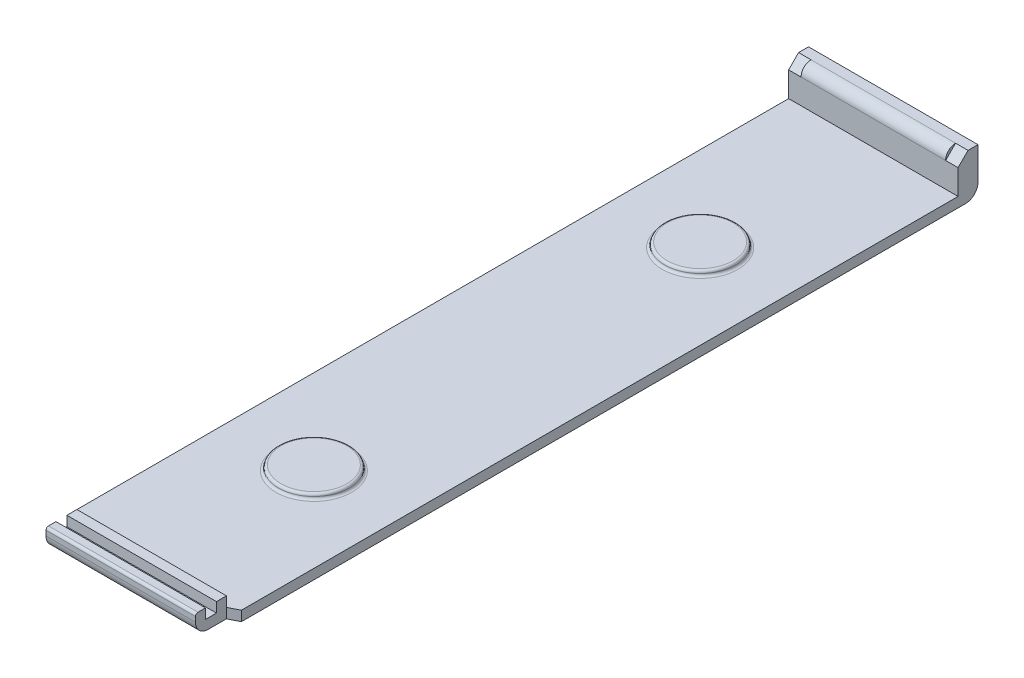
SolidWorks part; units mm, degrees
ref_plane "Front Plane" through (0, 0, 0) normal (0, 0, 1) x (1, 0, 0)
ref_plane "Top Plane" through (0, 0, 0) normal (0, 1, 0) x (1, 0, 0)
ref_plane "Right Plane" through (0, 0, 0) normal (1, 0, 0) x (0, 0, -1)
sketch "Sketch1" plane through (0, 0, 0) normal (0, 1, 0) x (1, 0, 0)
  line L1 (-19.5, 77.5) -> (19.5, 77.5)
  line L2 (-19.5, 77.5) -> (-19.5, -77.5)
  line L3 (-19.5, -77.5) -> (19.5, -77.5)
  line L4 (19.5, 77.5) -> (19.5, -77.5)
  line L5 (-19.5, 77.5) -> (19.5, -77.5) construction
  line L6 (-19.5, -77.5) -> (19.5, 77.5) construction
  point P0 (0, 0)
  dimension "D1" = 39
  dimension "D2" = 155
extrude "Boss-Extrude1" add sketch "Sketch1" along normal blind 2
sketch "Sketch2" plane through (0, 2, 0) normal (0, 1, 0) x (1, 0, 0)
  line L0 (-17.5, -75.5) -> (-17.5, -77.5)
  line L1 (-19.5, 77.5) -> (19.5, 77.5)
  line L2 (-19.5, 77.5) -> (-19.5, -77.5)
  line L3 (-19.5, -77.5) -> (19.5, -77.5)
  line L4 (19.5, 77.5) -> (19.5, -77.5)
  line L5 (-17.5, 75.5) -> (17.5, 75.5)
  line L6 (-17.5, 75.5) -> (-17.5, -75.5)
  line L7 (-17.5, -75.5) -> (17.5, -75.5)
  line L8 (17.5, 75.5) -> (17.5, -75.5)
  line L9 (-17.5, 75.5) -> (17.5, -75.5) construction
  line L10 (-17.5, -75.5) -> (17.5, 75.5) construction
  line L11 (17.5, -75.5) -> (17.5, -77.5)
  point P6 (0, 0)
  line M9 (19.5, -77.5) -> (19.5, 77.5)
  line M10 (19.5, 77.5) -> (-19.5, 77.5)
  line M11 (-19.5, 77.5) -> (-19.5, -77.5)
  line M12 (-19.5, -77.5) -> (19.5, -77.5)
  dimension "D1" = 2
  dimension "D2" = 2
extrude "Boss-Extrude2" add sketch "Sketch2" along normal blind 38 contours L8 L11 L3 L0 L6 L5 M9 M10 M11 M12 region at (-19.0983, 2, 76.5)
sketch "Sketch3" plane through (0, 2, 0) normal (0, 1, 0) x (1, 0, 0)
  line L0 (-17.5, 75.5) -> (-17.5, -77.5) construction
  line L1 (-17.5, -77.5) -> (-15.5, -77.5)
  line L2 (-17.5, -77.5) -> (-17.5, -75.5)
  line L3 (-17.5, -75.5) -> (-15.5, -75.5)
  line L4 (-15.5, -77.5) -> (-15.5, -75.5)
  line L5 (-17.5, -73.3) -> (-15.5, -73.3)
  line L6 (-17.5, -73.3) -> (-17.5, -71.3)
  line L7 (-17.5, -71.3) -> (-15.5, -71.3)
  line L8 (-15.5, -73.3) -> (-15.5, -71.3)
  line L9 (17.5, 75.5) -> (17.5, -77.5) construction
  line L10 (17.5, -77.5) -> (15.5, -77.5)
  line L11 (17.5, -77.5) -> (17.5, -75.5)
  line L12 (17.5, -75.5) -> (15.5, -75.5)
  line L13 (15.5, -77.5) -> (15.5, -75.5)
  line L14 (17.5, -73.3) -> (15.5, -73.3)
  line L15 (17.5, -73.3) -> (17.5, -71.3)
  line L16 (17.5, -71.3) -> (15.5, -71.3)
  line L17 (15.5, -73.3) -> (15.5, -71.3)
  line L18 (15.5, -75.5) -> (15.5, -73.3) construction
  line L19 (-15.5, -73.3) -> (15.5, -73.3) construction
  line L20 (-15.5, -75.5) -> (-15.5, -73.3) construction
  line L21 (-15.5, -75.5) -> (15.5, -75.5) construction
  line L22 (15.5, -71.3) -> (-15.5, -71.3) construction
  dimension "D1" = 2
  dimension "D2" = 2
  dimension "D3" = 2.2
  dimension "D4" = 2
extrude "Boss-Extrude3" add sketch "Sketch3" along normal up to surface (38 mm away) up to face at (0, 40, 0.5)
sketch "Sketch4" plane through (0, 0, -75.5) normal (0, 0, 1) x (1, 0, 0)
  line L0 (-17.5, 40) -> (-15.5, 40)
  line L1 (-17.5, 40) -> (17.5, 40) construction
  line L2 (-15.5, 40) -> (-15.5, 38)
  line L3 (-15.5, 38) -> (-17.5, 38)
  line L5 (-17.5, 38) -> (-17.5, 40)
  line L7 (-17.5, 40) -> (-17.5, 2) construction
  line L8 (-15.5, 33.8) -> (-17.5, 31.8)
  line L9 (-17.5, 31.8) -> (-17.5, 35.8)
  line L10 (-15.5, 33.8) -> (-15.5, 35.8)
  line L11 (-15.5, 35.8) -> (-17.5, 35.8)
  line L12 (0, 0) -> (0, 40) construction
  line L13 (15.5, 35.8) -> (17.5, 35.8)
  line L14 (15.5, 33.8) -> (15.5, 35.8)
  line L15 (17.5, 31.8) -> (17.5, 35.8)
  line L16 (15.5, 33.8) -> (17.5, 31.8)
  line L17 (17.5, 38) -> (17.5, 40)
  line L18 (15.5, 38) -> (17.5, 38)
  line L19 (15.5, 40) -> (15.5, 38)
  line L20 (17.5, 40) -> (15.5, 40)
  dimension "D1" = 2
  dimension "D2" = 2
  dimension "D3" = 45
  dimension "D4" = 2.2
  dimension "D5" = 2
extrude "Boss-Extrude4" add sketch "Sketch4" along normal up to surface (153 mm away) up to face at (0, 20.5, 77.5)
sketch "Sketch5" plane through (0, 2, 0) normal (0, 1, 0) x (1, 0, 0)
  line L1 (-15.5, -77.5) -> (15.5, -77.5)
  line L2 (-15.5, -77.5) -> (-15.5, -75.5)
  line L3 (-15.5, -75.5) -> (15.5, -75.5)
  line L4 (15.5, -77.5) -> (15.5, -75.5)
  line L5 (-15.5, -71.3) -> (15.5, -71.3)
  line L6 (-15.5, -71.3) -> (-15.5, -73.3)
  line L7 (-15.5, -73.3) -> (15.5, -73.3)
  line L8 (15.5, -71.3) -> (15.5, -73.3)
sketch "Sketch6" plane through (0, 0, -75.5) normal (0, 0, 1) x (1, 0, 0)
  line L0 (-17.5, 38) -> (-15.5, 38) construction
  line L1 (-17.5, 38) -> (17.5, 38)
  line L2 (-17.5, 38) -> (-17.5, 35.8)
  line L3 (-17.5, 35.8) -> (17.5, 35.8)
  line L4 (17.5, 38) -> (17.5, 35.8)
  line L5 (-17.5, 38) -> (-17.5, 35.8) construction
  line L6 (-15.5, 35.8) -> (-17.5, 35.8) construction
extrude "Cut-Extrude1" cut sketch "Sketch6" along normal through all
sketch "Sketch7" plane through (0, 2, 0) normal (0, 1, 0) x (1, 0, 0)
  line L1 (-17.5, -75.5) -> (17.5, -75.5)
  line L2 (-17.5, -75.5) -> (-17.5, -73.3)
  line L3 (-17.5, -73.3) -> (17.5, -73.3)
  line L4 (17.5, -75.5) -> (17.5, -73.3)
extrude "Cut-Extrude2" cut sketch "Sketch7" along normal through all
extrude "Boss-Extrude5" add sketch "Sketch5" along normal blind 2
sketch "Sketch8" plane through (0, 0, 0) normal (1, 0, 0) x (0, 0, -1)
  line L0 (75.5, 40) -> (73.5, 40)
  line L1 (-73.3, 40) -> (75.5, 40) construction
  line L2 (73.5, 40) -> (73.5, 38)
  line L3 (-73.3, 38) -> (75.5, 38) construction
  line L4 (73.5, 38) -> (75.5, 38)
  line L5 (75.5, 38) -> (75.5, 40)
  line L6 (75.5, 35.8) -> (73.5, 35.8)
  line L7 (-73.3, 35.8) -> (75.5, 35.8) construction
  line L8 (73.5, 35.8) -> (73.5, 33.8)
  line L9 (-71.3, 33.8) -> (75.5, 33.8) construction
  line L10 (73.5, 33.8) -> (75.5, 31.8)
  line L11 (75.5, 31.8) -> (75.5, 35.8)
  dimension "D1" = 2
extrude "Boss-Extrude6" add sketch "Sketch8" along normal up to surface and the other way up to surface up to face at (17.5, 16.9, -2.1) other way up to face at (-17.5, 16.9, -2.1)
sketch "Sketch10" plane through (-17.5, 0, 0) normal (1, 0, 0) x (0, 0, -1)
  line L1 (-75.5, 35.8) -> (-77.5, 35.8)
  line L2 (-75.5, 35.8) -> (-75.5, 38)
  line L3 (-75.5, 38) -> (-77.5, 38)
  line L4 (-77.5, 35.8) -> (-77.5, 38)
  line L5 (-73.3, 40) -> (-75.5, 40)
  line L6 (-73.3, 40) -> (-73.3, 38)
  line L7 (-73.3, 38) -> (-75.5, 38)
  line L8 (-75.5, 40) -> (-75.5, 38)
  line M1 (-75.5, 40) -> (-75.5, 38)
  line M2 (-75.5, 38) -> (-77.5, 38)
  line M3 (-77.5, 38) -> (-77.5, 35.8)
  line M4 (-77.5, 35.8) -> (-75.5, 35.8)
  line M11 (-73.3, 38) -> (-73.3, 40)
  line M12 (-73.3, 40) -> (-75.5, 40)
extrude "Boss-Extrude8" add sketch "Sketch10" along normal up to surface (2 mm away) contours L2 M4 M2 M3 | L7 M11 M12 M1 region at (-17.5, 39, 74.4) region at (-17.5, 36.9, 76.5) up to face at (-15.5, 39, -0.1)
sketch "Sketch11" plane through (17.5, 0, 0) normal (-1, 0, 0) x (0, 0, 1)
  line L1 (75.5, 35.8) -> (77.5, 35.8)
  line L2 (75.5, 35.8) -> (75.5, 38)
  line L3 (75.5, 38) -> (77.5, 38)
  line L4 (77.5, 35.8) -> (77.5, 38)
  line L5 (73.3, 40) -> (75.5, 40)
  line L6 (73.3, 40) -> (73.3, 38)
  line L7 (73.3, 38) -> (75.5, 38)
  line L8 (75.5, 40) -> (75.5, 38)
  line M2 (75.5, 35.8) -> (77.5, 35.8)
  line M3 (77.5, 35.8) -> (77.5, 38)
  line M4 (77.5, 38) -> (75.5, 38)
  line M5 (75.5, 38) -> (75.5, 40)
  line M6 (75.5, 40) -> (73.3, 40)
  line M7 (73.3, 40) -> (73.3, 38)
extrude "Boss-Extrude9" add sketch "Sketch11" along normal up to surface (2 mm away) contours L2 M2 M3 M4 | L7 M7 M5 M6 region at (17.5, 36.9, 76.5) region at (17.5, 39, 74.4) up to face at (15.5, 39, -0.1)
fillet "Fillet2" radius 2.5 17 edges at (-17.5, 16.9, 71.3) (17.5, 16.9, 71.3) (19.5, 20, 77.5) (-19.5, 20, 77.5) (-19.5, 20, -77.5) (-17.5, 16.9, -75.5) (17.5, 16.9, -75.5) (19.5, 20, -77.5) (-19.5, 40, 0) (0, 40, -77.5) (19.5, 40, 0) (0, 0, -77.5) (0, 0, 77.5) (-19.5, 0, 0) (19.5, 0, 0) (-17.5, 40, 77.5) (17.5, 40, 77.5)
sketch "Sketch13" plane through (0, 0, -77.5) normal (0, 0, -1) x (-1, 0, 0)
  line L0 (15.5, 37.5) -> (15.5, 4) construction
  line L1 (-15.5, 7) -> (15.5, 7)
  line L2 (-15.5, 7) -> (-15.5, 4)
  line L3 (-15.5, 4) -> (15.5, 4)
  line L4 (15.5, 7) -> (15.5, 4)
  dimension "D1" = 3
sketch "Sketch14" plane through (0, 0, -75.5) normal (0, 0, 1) x (1, 0, 0)
  line L1 (-18.25, 9) -> (18.25, 9)
  line L2 (-18.25, 9) -> (-18.25, 1.25)
  line L3 (-18.25, 1.25) -> (18.25, 1.25)
  line L4 (18.25, 9) -> (18.25, 1.25)
  line L5 (15.5, 7) -> (-15.5, 7) construction
  line L7 (17, 0) -> (17, 2.5) construction
  line L8 (19.5, 2.5) -> (17, 2.5) construction
  line L10 (-19.5, 2.5) -> (-17, 2.5) construction
  point P20 (17, 1.25)
  point P23 (18.25, 2.5)
  point P26 (-18.25, 2.5)
  dimension "D1" = 2
extrude "Boss-Extrude10" add sketch "Sketch14" along normal blind 2
extrude "Cut-Extrude4" cut sketch "Sketch13" against normal blind 2
fillet "Fillet3" radius 2 1 edges at (0, 9, -73.5)
fillet "Fillet4" radius 0.5 12 edges at (0, 4, -77.5) (0, 7, -77.5) (15.5, 7, -76.5) (15.5, 4, -76.5) (15.5, 5.5, -77.5) (-15.5, 4, -76.5) (-15.5, 7, -76.5) (-15.5, 5.5, -77.5) (0, 7, -75.5) (-15.5, 5.5, -75.5) (0, 4, -75.5) (15.5, 5.5, -75.5)
sketch "Sketch15" plane through (0, 0, 0) normal (0, -1, 0) x (1, 0, 0)
  line L0 (0, 77.5) -> (0, 0) construction
  line L1 (-17, 77.5) -> (17, 77.5) construction
  line L2 (0, 0) -> (0, -77.5) construction
  line L4 (17, -77.5) -> (-17, -77.5) construction
  circle A0 centre (0, 38.75) radius 5.1
  circle A1 centre (0, -38.75) radius 5.1
  dimension "D1" = 10.2
extrude "Cut-Extrude5" cut sketch "Sketch15" against normal through all
sketch "Sketch16" plane through (0, 2, 0) normal (0, 1, 0) x (1, 0, 0)
  circle A0 centre (0, 38.75) radius 7.1
  circle A1 centre (0, -38.75) radius 7.1
  circle A2 centre (0, 38.75) radius 5.1 construction
  dimension "D1" = 2
extrude "Boss-Extrude11" add sketch "Sketch16" along normal blind 1
fillet "Fillet5" radius 0.5 4 edges at (0, 2, 45.85) (0, 2, -31.65) (0, 3, 45.85) (0, 3, -31.65)
sketch "Sketch12" plane through (0, 0, -75.5) normal (0, 0, 1) x (1, 0, 0)
  line L0 (0, 0) -> (0, 40) construction
  line L1 (15.5, 40) -> (-15.5, 40) construction
  line L2 (0, 20) -> (-10, 20)
  line L3 (0, 20) -> (-9.0097, 15.6612)
  line L4 (0, 20) -> (-6.2349, 12.1817)
  line L5 (0, 20) -> (-2.2252, 10.2507)
  line L6 (0, 20) -> (2.2252, 10.2507)
  line L7 (0, 20) -> (6.2349, 12.1817)
  line L8 (0, 20) -> (9.0097, 15.6612)
  line L9 (0, 20) -> (10, 20)
  line L10 (0, 20) -> (9.0097, 24.3388)
  line L11 (0, 20) -> (6.2349, 27.8183)
  line L12 (0, 20) -> (2.2252, 29.7493)
  line L13 (0, 20) -> (-2.2252, 29.7493)
  line L14 (0, 20) -> (-6.2349, 27.8183)
  line L15 (0, 20) -> (-9.0097, 24.3388)
  circle A0 centre (0, 20) radius 10
  circle A1 centre (0, 20) radius 7.5
  circle A2 centre (0, 20) radius 5
  circle A3 centre (0, 20) radius 2.5
  point P26 (0, 20)
  dimension "D1" = 20
  dimension "D2" = 2.5
  dimension "D3" = 2.5
  dimension "D4" = 2.5
  dimension "D5" = 14
extrude "Cut-Extrude3" cut sketch "Sketch12" against normal through all contours A1 L6 A0 L7 | A1 L4 A0 L5 | A1 L2 A0 L3 | A1 L14 A0 L15 | A1 L0 A0 L13 | L0 A1 L12 A0 | A1 L10 A0 L11 | A1 L8 A0 L9 | A3 L8 A2 L9 | A3 L10 A2 L11 | L0 A3 L12 A2 | A3 L0 A2 L13 | A3 L14 A2 L15 | A3 L2 A2 L3 | A3 L4 A2 L5 | A3 L6 A2 L7 region at (-3.7903, 12.1293, -75.5) region at (3.7903, 12.1293, -75.5) region at (-1.6732, 16.5256, -75.5) region at (1.6732, 16.5256, -75.5) region at (-8.5168, 18.0561, -75.5) region at (8.5168, 18.0561, -75.5) region at (-0.4345, 23.8563, -75.5) region at (0.4345, 23.8563, -75.5) region at (-3.7596, 19.1419, -75.5) region at (3.7596, 19.1419, -75.5) region at (3.015, 22.4044, -75.5) region at (-3.015, 22.4044, -75.5) region at (-6.8299, 25.4467, -75.5) region at (6.8299, 25.4467, -75.5) region at (-0.9843, 28.7358, -75.5) region at (0.9843, 28.7358, -75.5)
fillet "Fillet6" radius 0.4 112 edges at (5.4555, 26.841, -77.5) (7.8183, 26.2349, -77.5) (7.8835, 23.7965, -77.5) (5.8637, 24.6762, -77.5) (3.75, 20, -77.5) (4.8746, 18.8874, -77.5) (3.3786, 18.3729, -77.5) (2.4373, 19.4437, -77.5) (-1.9471, 28.5306, -77.5) (0, 30, -77.5) (1.9471, 28.5306, -77.5) (0, 27.5, -77.5) (-7.8835, 16.2035, -77.5) (-9.7493, 17.7748, -77.5) (-8.75, 20, -77.5) (-7.312, 18.3311, -77.5) (2.3381, 17.0681, -77.5) (2.1694, 15.4952, -77.5) (0.8345, 16.344, -77.5) (1.0847, 17.7476, -77.5) (-0.8345, 16.344, -77.5) (-2.1694, 15.4952, -77.5) (-2.3381, 17.0681, -77.5) (-1.0847, 17.7476, -77.5) (5.4555, 13.159, -77.5) (4.3388, 10.9903, -77.5) (1.9471, 11.4694, -77.5) (3.2541, 13.2427, -77.5) (0, 22.5, -77.5) (-0.8345, 23.656, -77.5) (0, 25, -77.5) (0.8345, 23.656, -77.5) (-3.3786, 21.6271, -77.5) (-3.9092, 23.1174, -77.5) (-2.3381, 22.9319, -77.5) (-1.9546, 21.5587, -77.5) (-3.3786, 18.3729, -77.5) (-4.8746, 18.8874, -77.5) (-3.75, 20, -77.5) (-2.4373, 19.4437, -77.5) (-1.9471, 11.4694, -77.5) (-4.3388, 10.9903, -77.5) (-5.4555, 13.159, -77.5) (-3.2541, 13.2427, -77.5) (-7.8835, 23.7965, -77.5) (-7.8183, 26.2349, -77.5) (-5.4555, 26.841, -77.5) (-5.8637, 24.6762, -77.5) (2.3381, 22.9319, -77.5) (3.9092, 23.1174, -77.5) (3.3786, 21.6271, -77.5) (1.9546, 21.5587, -77.5) (8.75, 20, -77.5) (9.7493, 17.7748, -77.5) (7.8835, 16.2035, -77.5) (7.312, 18.3311, -77.5) (7.8835, 23.7965, -75.5) (7.8183, 26.2349, -75.5) (5.4555, 26.841, -75.5) (5.8637, 24.6762, -75.5) (3.3786, 18.3729, -75.5) (4.8746, 18.8874, -75.5) (3.75, 20, -75.5) (2.4373, 19.4437, -75.5) (1.9471, 28.5306, -75.5) (0, 30, -75.5) (-1.9471, 28.5306, -75.5) (0, 27.5, -75.5) (-8.75, 20, -75.5) (-9.7493, 17.7748, -75.5) (-7.8835, 16.2035, -75.5) (-7.312, 18.3311, -75.5) (0.8345, 16.344, -75.5) (2.1694, 15.4952, -75.5) (2.3381, 17.0681, -75.5) (1.0847, 17.7476, -75.5) (-2.3381, 17.0681, -75.5) (-2.1694, 15.4952, -75.5) (-0.8345, 16.344, -75.5) (-1.0847, 17.7476, -75.5) (1.9471, 11.4694, -75.5) (4.3388, 10.9903, -75.5) (5.4555, 13.159, -75.5) (3.2541, 13.2427, -75.5) (0, 22.5, -75.5) (0.8345, 23.656, -75.5) (0, 25, -75.5) (-0.8345, 23.656, -75.5) (-2.3381, 22.9319, -75.5) (-3.9092, 23.1174, -75.5) (-3.3786, 21.6271, -75.5) (-1.9546, 21.5587, -75.5) (-3.75, 20, -75.5) (-4.8746, 18.8874, -75.5) (-3.3786, 18.3729, -75.5) (-2.4373, 19.4437, -75.5) (-5.4555, 13.159, -75.5) (-4.3388, 10.9903, -75.5) (-1.9471, 11.4694, -75.5) (-3.2541, 13.2427, -75.5) (-5.4555, 26.841, -75.5) (-7.8183, 26.2349, -75.5) (-7.8835, 23.7965, -75.5) (-5.8637, 24.6762, -75.5) (3.3786, 21.6271, -75.5) (3.9092, 23.1174, -75.5) (2.3381, 22.9319, -75.5) (7.8835, 16.2035, -75.5) (9.7493, 17.7748, -75.5) (8.75, 20, -75.5) (7.312, 18.3311, -75.5) (1.9546, 21.5587, -75.5)
fillet "Fillet7" radius 0.5 8 edges at (15.5, 40, 0.75) (15.5, 39.2678, 76.7678) (-15.5, 40, 0.75) (-15.5, 39.2678, 76.7678) (0, 40, -73.5) (15.5, 20.75, 77.5) (-15.5, 20.75, 77.5) (0, 4, 77.5)
sketch "Sketch20" plane through (0, 0, 0) normal (1, 0, 0) x (0, 0, -1)
  line L1 (75.5, 9) -> (77.5, 9)
  line L2 (77.5, 2.5) -> (77.5, 37.5) construction
  line L3 (77.5, 9) -> (77.5, 0)
  line L4 (77.5, 0) -> (-77.5, 0)
  line L5 (-77.5, 0) -> (-77.5, 4)
  line L6 (-75.5, 4) -> (-77.5, 4)
  line L7 (-75.5, 4) -> (73.5, 4)
  line L8 (73.5, 2) -> (73.5, 7) construction
  line L9 (73.5, 4) -> (73.5, 9)
  line L10 (73.5, 9) -> (75.5, 9)
  line L11 (-77.5, 4) -> (-77.5, 40)
  line L12 (-77.5, 40) -> (77.5, 40)
  line L13 (77.5, 40) -> (77.5, 9)
  dimension "D1" = 40
extrude "Cut-Extrude8" cut sketch "Sketch20" against normal through all both and the other way through all contours L13 L12 L11 L6 L7 L9 L10 L1 region at (0, 22.0558, 0.2716)
sketch "Sketch21" plane through (0, 0, 0) normal (0, 1, 0) x (1, 0, 0)
  line L0 (17, 77.5) -> (17, 73.5)
  line L1 (17, 77.5) -> (17, 75) construction
  line L4 (-17.4495, 73.5) -> (17.4495, 73.5) construction
  line L9 (17, -77.5) -> (19.5, -77.5)
  line L10 (19.5, -77.5) -> (19.5, 77.5)
  line L11 (19.5, 77.5) -> (17, 77.5)
  line L12 (19.5, 73.5) -> (19.5, -75) construction
  line L13 (16, -77.5) -> (17, -77.5) construction
  line L14 (0, 0) -> (0, -71.3) construction
  line L15 (15, -71.3) -> (-15, -71.3) construction
  line L24 (17, 73.5) -> (17, -77.5)
  line L25 (-17, 73.5) -> (-17, -77.5)
  line L26 (-19.5, 77.5) -> (-17, 77.5)
  line L27 (-19.5, -77.5) -> (-19.5, 77.5)
  line L28 (-17, -77.5) -> (-19.5, -77.5)
  line L29 (-17, 77.5) -> (-17, 73.5)
  line L30 (-17, -77.5) -> (17, -77.5)
  line L31 (-17, 77.5) -> (17, 77.5)
  arc A0 (19.5, 75) -> (17, 77.5) centre (17, 75) ccw construction
extrude "Cut-Extrude11" cut sketch "Sketch21" along normal through all contours L0 L24 L9 L10 L11 | L29 L26 L27 L28 L25 region at (18.25, 0, 0) region at (-18.25, 0, 0)
sketch "Sketch24" plane through (0, 0, 0) normal (0, 1, 0) x (1, 0, 0)
  line L9 (17, -77.5) -> (15, -77.5)
  line L10 (16, -77.5) -> (-16, -77.5) construction
  line L11 (15, -77.5) -> (15, -71.3)
  line L12 (15, -71.3) -> (17, -70.3)
  line L13 (17, -70.3) -> (17, -77.5)
  line L14 (0, 0) -> (0, -31.15) construction
  line L15 (-17, -70.3) -> (-17, -77.5)
  line L16 (-15, -71.3) -> (-17, -70.3)
  line L17 (-15, -77.5) -> (-15, -71.3)
  line L18 (-17, -77.5) -> (-15, -77.5)
  circle A1 centre (0, -38.75) radius 7.6 construction
extrude "Cut-Extrude12" cut sketch "Sketch24" along normal through all
sketch "Sketch26" plane through (17, 0, 0) normal (1, 0, 0) x (0, 0, -1)
  line L0 (75.5, 9) -> (73.5, 7)
  line L1 (77.5, 9) -> (74.5, 9) construction
  line L2 (73.5, 7) -> (73.5, 9)
  line L3 (73.5, 9) -> (75.5, 9)
  point P6 (0, 0)
extrude "Cut-Extrude13" cut sketch "Sketch26" against normal blind 2.5
mirror "Mirror1" about plane through (0, 0, 0) normal (1, 0, 0) of "Cut-Extrude13"
